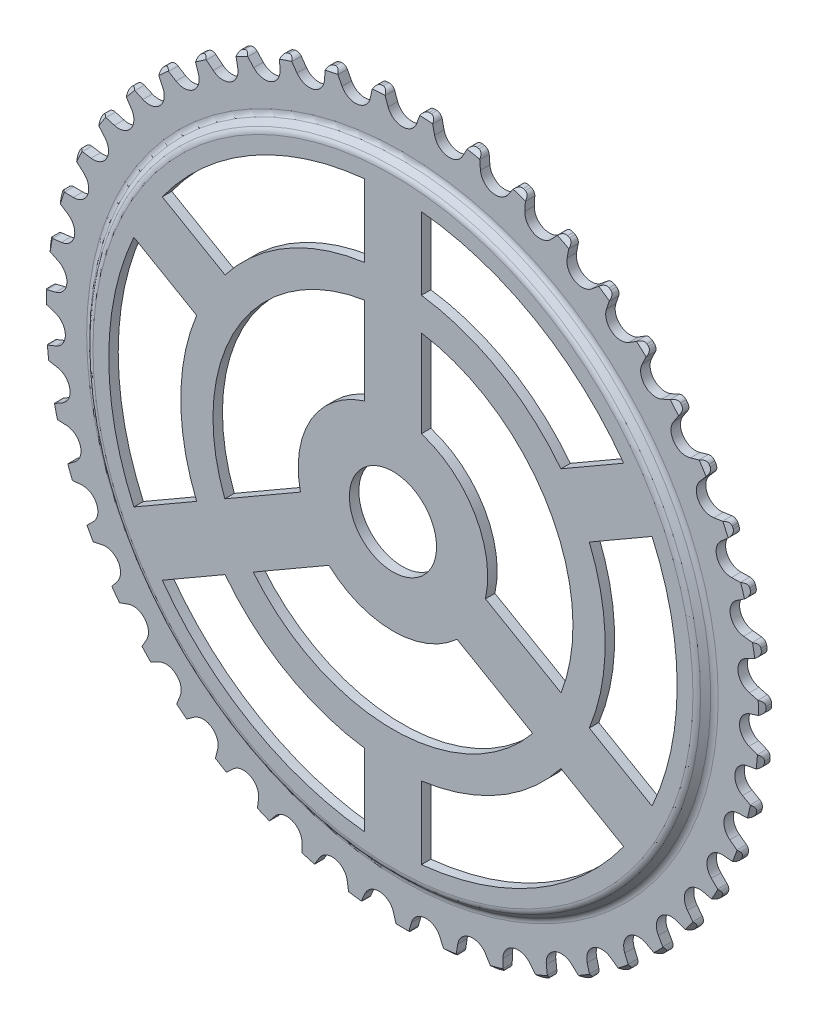
SolidWorks part; units mm, degrees
ref_plane "Alzado" through (0, 0, 0) normal (0, 0, 1) x (1, 0, 0)
ref_plane "Planta" through (0, 0, 0) normal (0, 1, 0) x (1, 0, 0)
ref_plane "Vista lateral" through (0, 0, 0) normal (1, 0, 0) x (0, 0, -1)
sketch "Croquis1" plane through (0, 0, 0) normal (1, 0, 0) x (0, 0, -1)
  line L0 (0, 11.5) -> (0, 80)
  line L1 (0, 80) -> (2.5, 82.5)
  line L2 (2.5, 82.5) -> (2.5, 95)
  line L3 (2.5, 95) -> (5, 95)
  line L4 (5, 95) -> (5, 81.4645)
  line L5 (5, 81.4645) -> (2.5, 78.9645)
  line L6 (2.5, 78.9645) -> (2.5, 11.5)
  line L7 (2.5, 11.5) -> (0, 11.5)
  line L8 (0, 0) -> (50, 0) construction
  dimension "D1" = 11.5
  dimension "D2" = 2.5
  dimension "D3" = 2.5
  dimension "D4" = 95
  dimension "D5" = 12.5
  dimension "D6" = 135
  dimension "D7" = 5
  dimension "D8" = 2.5
  dimension "D9" = 50
revolve "Revolución1" add sketch "Croquis1" angle 360 about L8
sketch "Croquis2" plane through (0, 0, 0) normal (0, 0, 1) x (1, 0, 0)
  line L0 (7.5, 23.8485) -> (7.5, 46.9042)
  line L1 (24.4034, -5.429) -> (44.3702, -16.9569)
  line L2 (0, 0) -> (82.2724, -47.5) construction
  line L3 (0, 0) -> (0, 95) construction
  arc A0 (24.4034, -5.429) -> (7.5, 23.8485) centre (0, 0) ccw
  arc A1 (44.3702, -16.9569) -> (7.5, 46.9042) centre (0, 0) ccw
  circle A2 centre (0, 0) radius 95 construction
  dimension "D1" = 50
  dimension "D2" = 95
  dimension "D3" = 7.5
  dimension "D4" = 120
  dimension "D5" = 7.5
extrude "Cortar-Extruir1" cut sketch "Croquis2" against normal through all contours A1 L0 A0 L1
pattern_circular "MatrizC1" count 3 every 120 about axis through (0, 0, 0) along (0, 0, 1) of "Cortar-Extruir1"
sketch "Croquis3" plane through (0, 0, 0) normal (0, 0, 1) x (1, 0, 0)
  line L0 (7.5, 74.6241) -> (7.5, 55.4955)
  line L1 (44.3105, 34.2429) -> (60.8763, 43.8072)
  line L2 (0, 0) -> (69.282, 40) construction
  line L4 (0, 0) -> (0, 80) construction
  arc A0 (44.3105, 34.2429) -> (7.5, 55.4955) centre (0, 0) ccw
  arc A1 (60.8763, 43.8072) -> (7.5, 74.6241) centre (0, 0) ccw
  circle A2 centre (0, 0) radius 80 construction
  dimension "D1" = 112
  dimension "D2" = 150
  dimension "D3" = 7.5
  dimension "D4" = 60
  dimension "D5" = 7.5
extrude "Cortar-Extruir2" cut sketch "Croquis3" against normal through all
pattern_circular "MatrizC2" count 6 over 360 about axis through (0, 0, -2.5) along (0, 0, 1) of "Cortar-Extruir2"
chamfer "Chaflán1" distance 1 angle 45 1 edges at (95, 0, -2.5)
sketch "Croquis5" plane through (0, 0, -2.5) normal (0, 0, 1) x (1, 0, 0)
  line L0 (3.7588, 91.6319) -> (8.8063, 105.5)
  line L1 (8.8063, 105.5) -> (-8.8063, 105.5)
  line L2 (0, 105.5) -> (0, 93) construction
  line L3 (-3.7588, 91.6319) -> (-8.8063, 105.5)
  arc A0 (-3.7588, 91.6319) -> (3.7588, 91.6319) centre (0, 93) ccw
  dimension "D1" = 8
  dimension "D2" = 93
  dimension "D3" = 20
  dimension "D4" = 12.5
extrude "Cortar-Extruir3" cut sketch "Croquis5" against normal through all
pattern_circular "MatrizC3" count 47 over 360 about axis through (0, 0, 0) along (0, 0, 1) of "Cortar-Extruir3"
fillet "Redondeo1" radius 1.5 94 edges at (4.9379, 94.8716, -4.25) (7.7513, 94.6832, -4.25) (-20.3022, 92.8053, -4.25) (-29.8271, 90.1961, -4.25) (-32.4908, 89.2712, -4.25) (-41.5829, 85.4158, -4.25) (-44.0996, 84.1441, -4.25) (-52.5967, 79.1112, -4.25) (-54.9214, 77.5154, -4.25) (-62.6719, 71.3949, -4.25) (-64.7631, 69.5035, -4.25) (-71.6287, 62.4045, -4.25) (-73.4492, 60.2513, -4.25) (-79.3073, 52.3005, -4.25) (-80.8246, 49.9239, -4.25) (-85.5707, 41.2633, -4.25) (-86.7576, 38.7055, -4.25) (-90.307, 29.4896, -4.25) (-91.1424, 26.7965, -4.25) (-93.4319, 17.1897, -4.25) (-93.9009, 14.4093, -4.25) (-94.8894, 4.5831, -4.25) (-94.9836, 1.765, -4.25) (-94.6536, -8.1053, -4.25) (-94.3714, -10.9108, -4.25) (-92.7287, -20.6491, -4.25) (-92.0751, -23.3919, -4.25) (-89.1491, -32.8243, -4.25) (-88.1357, -35.4556, -4.25) (-83.9786, -44.4139, -4.25) (-4.9379, 94.8716, -4.25) (-7.7513, 94.6832, -4.25) (-17.539, 93.3669, -4.25) (-82.6235, -46.8866, -4.25) (-77.3095, -55.2109, -4.25) (-75.6369, -57.4809, -4.25) (-67.3006, -67.0494, -4.25) (-69.2608, -65.0226, -4.25) (-59.9762, -73.674, -4.25) (-57.7633, -75.4215, -4.25) (-49.6213, -81.0107, -4.25) (-47.1952, -82.4476, -4.25) (-38.3809, -86.9017, -4.25) (-35.7849, -88.0025, -4.25) (-26.4555, -91.242, -4.25) (-23.7361, -91.987, -4.25) (-14.0581, -93.9541, -4.25) (-11.2636, -94.3299, -4.25) (-1.4098, -94.9895, -4.25) (1.4098, -94.9895, -4.25) (11.2636, -94.3299, -4.25) (14.0581, -93.9541, -4.25) (23.7361, -91.987, -4.25) (26.4555, -91.242, -4.25) (35.7849, -88.0025, -4.25) (38.3809, -86.9017, -4.25) (47.1952, -82.4476, -4.25) (49.6213, -81.0107, -4.25) (57.7633, -75.4215, -4.25) (59.9762, -73.674, -4.25) (67.3006, -67.0494, -4.25) (69.2608, -65.0226, -4.25) (75.6369, -57.4809, -4.25) (77.3095, -55.2109, -4.25) (82.6235, -46.8866, -4.25) (83.9786, -44.4139, -4.25) (88.1357, -35.4556, -4.25) (89.1491, -32.8243, -4.25) (92.0751, -23.3919, -4.25) (92.7287, -20.6491, -4.25) (94.3714, -10.9108, -4.25) (94.6536, -8.1053, -4.25) (94.9836, 1.765, -4.25) (94.8894, 4.5831, -4.25) (93.9009, 14.4093, -4.25) (93.4319, 17.1897, -4.25) (91.1424, 26.7965, -4.25) (90.307, 29.4896, -4.25) (86.7576, 38.7055, -4.25) (85.5707, 41.2633, -4.25) (80.8246, 49.9239, -4.25) (79.3073, 52.3005, -4.25) (73.4492, 60.2513, -4.25) (71.6287, 62.4045, -4.25) (64.7631, 69.5035, -4.25) (62.6719, 71.3949, -4.25) (54.9214, 77.5154, -4.25) (52.5967, 79.1112, -4.25) (44.0996, 84.1441, -4.25) (41.5829, 85.4158, -4.25) (32.4908, 89.2712, -4.25) (29.8271, 90.1961, -4.25) (17.539, 93.3669, -4.25) (20.3022, 92.8053, -4.25)
fillet "Redondeo2" radius 2 4 edges at (80, 0, 0) (81.4645, 0, -5) (82.5, 0, -2.5) (78.9645, 0, -2.5)
ref_plane "Plane1" through (0, 0, -3.75) normal (0, 0, 1) x (1, 0, 0)
